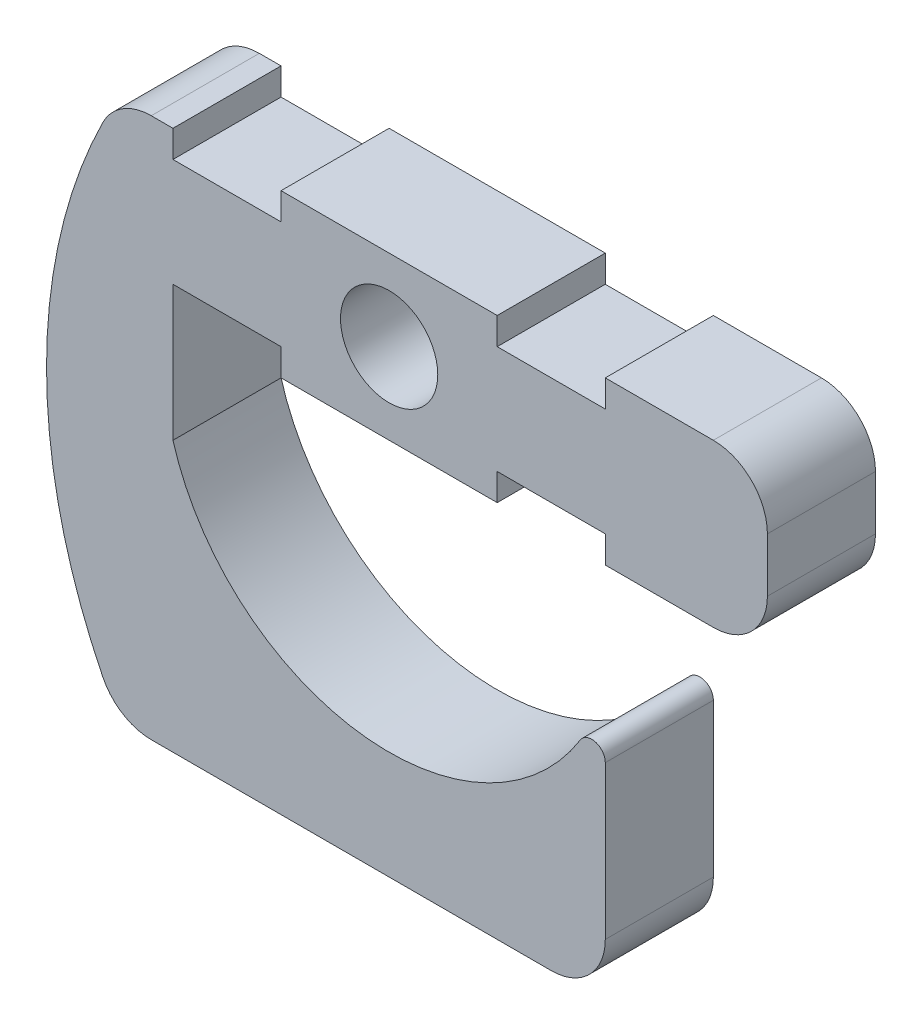
SolidWorks part; units mm, degrees
material "ABS"
ref_plane "Front Plane" through (0, 0, 0) normal (0, 0, 1) x (1, 0, 0)
ref_plane "Top Plane" through (0, 0, 0) normal (0, 1, 0) x (1, 0, 0)
ref_plane "Right Plane" through (0, 0, 0) normal (1, 0, 0) x (0, 0, -1)
sketch "Sketch1" plane through (0, 0, 0) normal (0, 0, 1) x (1, 0, 0)
  line L1 (-12.7, -3.81) -> (17.78, -3.81)
  line L2 (-12.7, -3.81) -> (-12.7, 3.81)
  line L3 (-12.7, 3.81) -> (17.78, 3.81)
  line L4 (17.78, -3.81) -> (17.78, 3.81)
  line L5 (-12.7, -3.81) -> (17.78, 3.81) construction
  line L6 (-12.7, 3.81) -> (17.78, -3.81) construction
  line L7 (-12.7, -3.81) -> (-10.16, -3.81)
  line L8 (-12.7, -3.81) -> (-12.7, -16.51)
  line L9 (-12.7, -16.51) -> (-10.16, -16.51)
  line L10 (-10.16, -3.81) -> (-10.16, -16.51)
  line L11 (-12.7, -16.51) -> (10.16, -16.51)
  line L12 (-12.7, -16.51) -> (-12.7, -21.59)
  line L13 (-12.7, -21.59) -> (10.16, -21.59)
  line L14 (10.16, -16.51) -> (10.16, -21.59)
  line L15 (10.16, -16.51) -> (23.1865, -16.51)
  line L16 (10.16, -16.51) -> (10.16, -8.89)
  line L22 (-12.7, 3.81) -> (-12.7, -21.59)
  circle A0 centre (0, 0) radius 2.286
  arc A1 (10.16, -8.89) -> (-10.16, -8.89) centre (0, -5.9267) cw
  arc A2 (-12.7, 3.81) -> (-12.7, -21.59) centre (9.297, -8.89) ccw
  point P0 (0, 0)
  point P14 (10.16, -19.05)
  point P19 (2.54, 0)
  dimension "D3" = 4.572
  dimension "D7" = 2.54
  dimension "D9" = 25.4
  dimension "D1" = 30.48
  dimension "D2" = 7.62
  dimension "D4" = 12.7
  dimension "D5" = 10.16
  dimension "D6" = 5.08
  dimension "D8" = 7.62
  dimension "D10" = 20.32
extrude "Boss-Extrude1" add sketch "Sketch1" along normal mid plane 5.08 contours L1 L4 L3 L2 A0 | L12 L8 L2 | L10 L1 L8 L9 | L14 L11 L9 L12 L13 | L11 L10 | L11 | L11 L16 region at (2.7332, 0, 0) region at (-14.0693, -8.89, 0) region at (-11.43, -10.16, 0) region at (-1.27, -19.05, 0) region at (-7.8335, -14.4966, 0) region at (7.8335, -14.4966, 0)
fillet "Fillet1" radius 2.54 5 edges at (17.78, 3.81, 0) (17.78, -3.81, 0) (10.16, -21.59, 0) (-12.7, -21.59, 0) (-12.7, 3.81, 0)
fillet "Fillet2" radius 5.08 1 edges at (-10.16, -3.81, 0)
sketch "Sketch2" plane through (0, 0, 2.54) normal (0, 0, 1) x (1, 0, 0)
  line L0 (-5.08, -3.81) -> (15.24, -3.81) construction
  line L1 (-5.08, -3.81) -> (-10.16, -3.81)
  line L2 (-5.08, -3.81) -> (-5.08, -2.54)
  line L3 (-5.08, -2.54) -> (-10.16, -2.54)
  line L4 (-10.16, -3.81) -> (-10.16, -2.54)
  line L5 (-11.1811, 3.81) -> (15.24, 3.81) construction
  line L6 (-5.08, 3.81) -> (-10.16, 3.81)
  line L7 (-5.08, 3.81) -> (-5.08, 2.54)
  line L8 (-5.08, 2.54) -> (-10.16, 2.54)
  line L9 (-10.16, 3.81) -> (-10.16, 2.54)
  line L10 (0, -2.794) -> (0, 2.794) construction
  line L11 (5.08, -3.81) -> (5.08, -2.54)
  line L12 (10.16, -3.81) -> (10.16, -2.54)
  line L13 (5.08, -2.54) -> (10.16, -2.54)
  line L14 (5.08, 2.54) -> (10.16, 2.54)
  line L15 (10.16, 3.81) -> (10.16, 2.54)
  line L16 (5.08, 3.81) -> (5.08, 2.54)
  line L17 (-10.16, -3.81) -> (-10.16, -8.89)
  arc A0 (-5.08, -3.81) -> (-10.16, -8.89) centre (-5.08, -8.89) ccw construction
  line M9 (15.24, 3.81) -> (-11.1811, 3.81)
  arc M26 (-10.16, -8.89) -> (-5.08, -3.81) centre (-5.08, -8.89) cw
  line M27 (-5.08, -3.81) -> (15.24, -3.81)
  dimension "D1" = 5.08
  dimension "D2" = 5.08
  dimension "D3" = 1.27
extrude "Cut-Extrude1" cut sketch "Sketch2" against normal through all contours L9 L8 L7 M9 | L4 L1 L2 L3 M27 | L16 L14 L15 M9 | L13 L11 L12 M27 | L1 L17 M26 | L4 L3 L2 L1 region at (-9.0253, -4.9447, 2.54) region at (-7.62, -3.175, 2.54) region at (7.62, -3.175, 2.54) region at (-7.62, 3.175, 2.54) region at (7.62, 3.175, 2.54)
fillet "Fillet3" radius 0.635 1 edges at (10.16, -8.89, 0)
